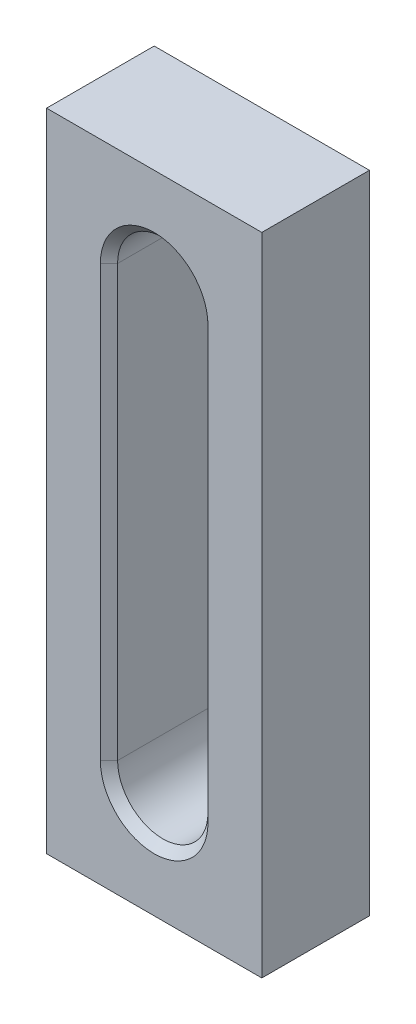
SolidWorks part; units mm, degrees
material "Простая углеродистая сталь"
ref_plane "Спереди" through (0, 0, 0) normal (0, 0, 1) x (1, 0, 0)
ref_plane "Сверху" through (0, 0, 0) normal (0, 1, 0) x (1, 0, 0)
ref_plane "Справа" through (0, 0, 0) normal (1, 0, 0) x (0, 0, -1)
sketch "Эскиз1" plane through (0, 0, 0) normal (0, 0, 1) x (1, 0, 0)
  line L1 (0, 0) -> (50, 0)
  line L2 (0, 0) -> (0, 150)
  line L3 (0, 150) -> (50, 150)
  line L4 (50, 0) -> (50, 150)
  dimension "D1" = 50
  dimension "D2" = 150
extrude "Бобышка-Вытянуть1" add sketch "Эскиз1" along normal blind 25
sketch "Эскиз2" plane through (0, 0, 25) normal (0, 0, 1) x (1, 0, 0)
  line L0 (35.5, 125) -> (35.5, 25)
  line L1 (14.5, 125) -> (14.5, 25)
  line L3 (0, 150) -> (0, 0) construction
  line L4 (0, 0) -> (50, 0) construction
  arc A0 (14.5, 25) -> (35.5, 25) centre (25, 25) ccw
  arc A1 (14.5, 125) -> (35.5, 125) centre (25, 125) cw
  point P3 (0, 0)
  point P4 (0, 0)
  dimension "D1" = 25
  dimension "D2" = 25
  dimension "D3" = 21
extrude "Вырез-Вытянуть1" cut sketch "Эскиз2" against normal through all
chamfer "Фаска1" distance 2 angle 45 8 edges at (14.5, 75, 0) (25, 14.5, 0) (25, 135.5, 0) (35.5, 75, 0) (35.5, 75, 25) (25, 135.5, 25) (25, 14.5, 25) (14.5, 75, 25)
